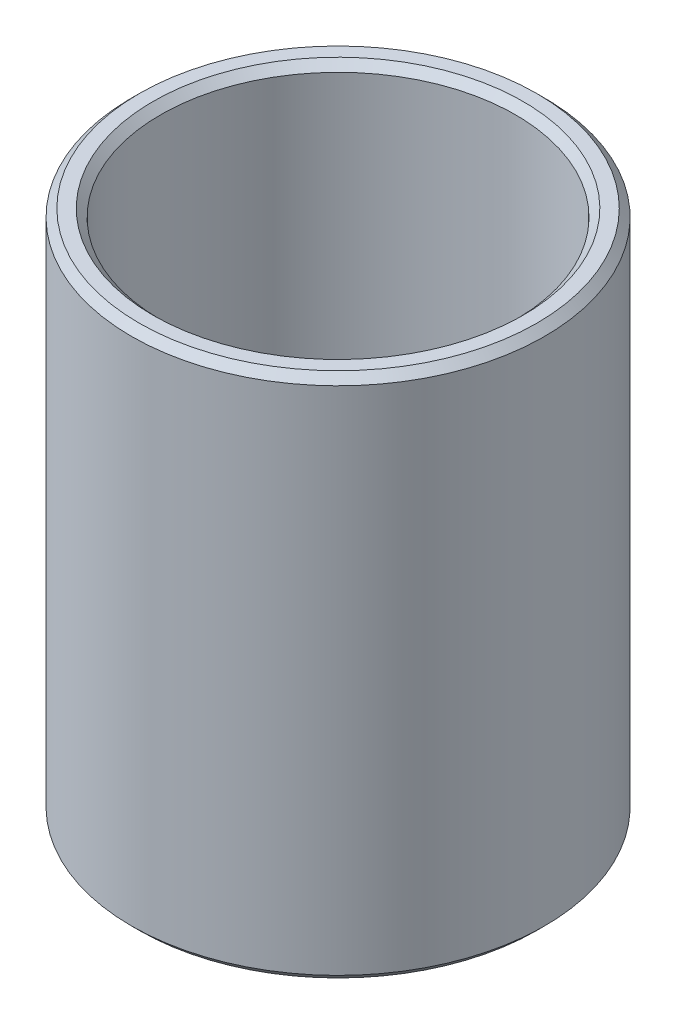
SolidWorks part; units mm, degrees
ref_plane "Front Plane" through (0, 0, 0) normal (0, 0, 1) x (1, 0, 0)
ref_plane "Top Plane" through (0, 0, 0) normal (0, 1, 0) x (1, 0, 0)
ref_plane "Right Plane" through (0, 0, 0) normal (1, 0, 0) x (0, 0, -1)
sketch "Sketch1" plane through (0, 0, 0) normal (0, 1, 0) x (1, 0, 0)
  circle A0 centre (0, 0) radius 30
  dimension "SLEEVE_OD" = 60
extrude "Boss-Extrude1" add sketch "Sketch1" along normal blind 76.3998
sketch "Sketch2" plane through (0, 0, 0) normal (0, 1, 0) x (1, 0, 0)
  circle A0 centre (0, 0) radius 25.7836
  dimension "BORE_D" = 51.5673
extrude "Cut-Extrude1" cut sketch "Sketch2" along normal through all
chamfer "Chamfer1" distance 1.1117 angle 45 4 edges at (0, 76.3998, 25.7836) (0, 0, 25.7836) (0, 0, 30) (0, 76.3998, 30)
